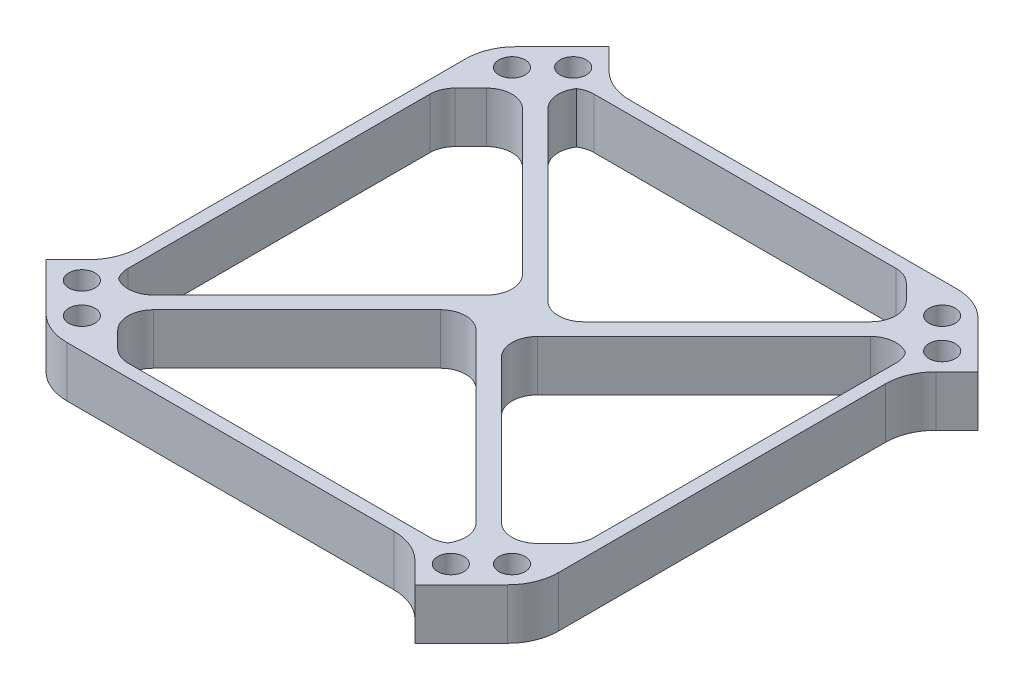
SolidWorks part; units mm, degrees
ref_plane "Front Plane" through (0, 0, 0) normal (0, 0, 1) x (1, 0, 0)
ref_plane "Top Plane" through (0, 0, 0) normal (0, 1, 0) x (1, 0, 0)
ref_plane "Right Plane" through (0, 0, 0) normal (1, 0, 0) x (0, 0, -1)
sketch "Sketch1" plane through (0, 0, 0) normal (0, 1, 0) x (1, 0, 0)
  line L0 (-55.533, 36.3909) -> (-36.3909, 55.533) construction
  line L1 (-36.3909, 55.533) -> (36.3909, 55.533) construction
  line L2 (36.3909, 55.533) -> (55.533, 36.3909) construction
  line L3 (55.533, 36.3909) -> (55.533, -36.3909) construction
  line L4 (55.533, -36.3909) -> (36.3909, -55.533) construction
  line L5 (36.3909, -55.533) -> (-36.3909, -55.533) construction
  line L6 (-36.3909, -55.533) -> (-55.533, -36.3909) construction
  line L7 (-55.533, -36.3909) -> (-55.533, 36.3909) construction
  line L8 (0, 0) -> (0, 31.0491) construction
  line L9 (0, 0) -> (32.6609, 0) construction
  line L10 (-48.4619, 43.4619) -> (-36.3909, 55.533)
  line L11 (-45.9619, -45.9619) -> (45.9619, -45.9619) construction
  line L12 (-45.9619, -45.9619) -> (-45.9619, 45.9619) construction
  line L13 (-45.9619, 45.9619) -> (45.9619, 45.9619) construction
  line L14 (45.9619, -45.9619) -> (45.9619, 45.9619) construction
  line L15 (-36.3909, 55.533) -> (-29.3198, 48.4619)
  line L16 (-29.3198, 48.4619) -> (43.4619, 48.4619)
  line L17 (43.4619, 48.4619) -> (55.533, 36.3909)
  line L18 (55.533, 36.3909) -> (48.4619, 29.3198)
  line L19 (48.4619, 29.3198) -> (48.4619, -43.4619)
  line L20 (48.4619, -43.4619) -> (36.3909, -55.533)
  line L21 (36.3909, -55.533) -> (29.3198, -48.4619)
  line L22 (29.3198, -48.4619) -> (-43.4619, -48.4619)
  line L23 (-43.4619, -48.4619) -> (-55.533, -36.3909)
  line L24 (-55.533, -36.3909) -> (-48.4619, -29.3198)
  line L25 (-48.4619, -29.3198) -> (-48.4619, 43.4619)
  point P18 (-45.9619, 45.9619)
  dimension "D1" = 65
  dimension "D2" = 10
  dimension "D3" = 2.5
extrude "Boss-Extrude1" add sketch "Sketch1" along normal blind 10
sketch "Sketch2" plane through (0, 10, 0) normal (0, 1, 0) x (1, 0, 0)
  line L0 (0, 0) -> (0, 27.7289) construction
  line L1 (48.4619, -48.4619) -> (-48.4619, -48.4619) construction
  line L2 (-48.4619, 43.4619) -> (-48.4619, -29.3198) construction
  line L3 (48.4619, 48.4619) -> (-48.4619, 48.4619) construction
  line L4 (-48.4619, -48.4619) -> (-48.4619, 48.4619) construction
  line L5 (0, 0) -> (26.129, 0) construction
  line L10 (-2.5, 4.5711) -> (-42.4264, -35.3553)
  line L11 (-45.9619, 31.8198) -> (-37.8553, 39.9264)
  line L12 (-37.8553, 39.9264) -> (-2.5, 4.5711)
  line L13 (-42.4264, -35.3553) -> (-45.9619, -31.8198)
  line L15 (43.4619, 48.4619) -> (-29.3198, 48.4619) construction
  line L16 (-43.4619, -48.4619) -> (29.3198, -48.4619) construction
  line L17 (48.4619, 48.4619) -> (48.4619, -48.4619) construction
  line L18 (48.4619, -43.4619) -> (48.4619, 29.3198) construction
  line L19 (-36.3909, 55.533) -> (-48.4619, 43.4619) construction
  line L20 (-45.9619, -31.8198) -> (-45.9619, 31.8198)
  line L21 (-48.4619, -29.3198) -> (-45.9619, -31.8198) construction
  dimension "D1" = 10
  dimension "D2" = 5
  dimension "D3" = 5
  dimension "D4" = 2.5
extrude "Cut-Extrude1" cut sketch "Sketch2" against normal through all
ref_axis "Axis2" through (0, 10.5, 0) along (0, -1, 0)
fillet "Fillet4" radius 5 5 edges at (-37.8553, 5, -39.9264) (-2.5, 5, -4.5711) (-45.9619, 5, 31.8198) (-42.4264, 5, 35.3553) (-45.9619, 5, -31.8198)
pattern_circular "CirPattern6" count 4 over 360 about axis through (0, 10.5, 0) along (0, -1, 0) of "Cut-Extrude1", "Fillet4"
fillet "Fillet5" radius 10 8 edges at (43.4619, 5, -48.4619) (-29.3198, 5, -48.4619) (-48.4619, 5, -43.4619) (-48.4619, 5, 29.3198) (-43.4619, 5, 48.4619) (29.3198, 5, 48.4619) (48.4619, 5, -29.3198) (48.4619, 5, 43.4619)
hole_wizard "#6 (0.204) Diameter Hole1" positions "Sketch3" profile "Sketch4" hole size "#6" standard "ANSI Inch" end condition through all
sketch "Sketch3" plane through (0, 10, 0) normal (0, 1, 0) x (1, 0, 0)
  line L1 (42.4264, -42.4264) -> (-42.4264, -42.4264) construction
  line L2 (42.4264, -42.4264) -> (42.4264, 42.4264) construction
  line L3 (42.4264, 42.4264) -> (-42.4264, 42.4264) construction
  line L4 (-42.4264, -42.4264) -> (-42.4264, 42.4264) construction
  line L5 (0, 0) -> (0, 27.9091) construction
  line L7 (0, 0) -> (26.5726, 0) construction
  line L9 (-36.3909, 55.533) -> (-45.533, 46.3909) construction
  line L11 (-43.4619, 48.4619) -> (-36.3909, 55.533) construction
  line L12 (-43.4619, 48.4619) -> (-36.3909, 41.3909) construction
  line L13 (-36.3909, 55.533) -> (-29.3198, 48.4619) construction
  line L16 (-36.3909, 41.3909) -> (-36.3909, 55.533) construction
  line L18 (-43.4619, 48.4619) -> (-29.3198, 48.4619) construction
  line L20 (-29.3198, 48.4619) -> (-36.3909, 41.3909) construction
  line L22 (-41.3909, 36.3909) -> (-44.4975, 33.2843) construction
  point P3 (-42.4264, 42.4264)
  point P355 (-36.3909, 48.4619)
  dimension "D1" = 5
  dimension "D2" = 60
sketch "Sketch4" plane through (-42.4264, 10, -42.4264) normal (1, 0, 0) x (0, 0, 1)
  line L0 (0, 0) -> (0, 10)
  line L1 (0, 10) -> (2.5908, 10)
  line L2 (2.5908, 10) -> (2.5908, 0)
  line L5 (2.5908, 0) -> (0, 0)
  line L11 (0, -6.35) -> (0, 107.95) construction
  dimension "Thru Hole Dia." = 5.1816
  dimension "Thru Hole Depth" = 10
pattern_circular "CirPattern7" count 4 over 360 about axis through (0, 10.5, 0) along (0, -1, 0) of "#6 (0.204) Diameter Hole1"
